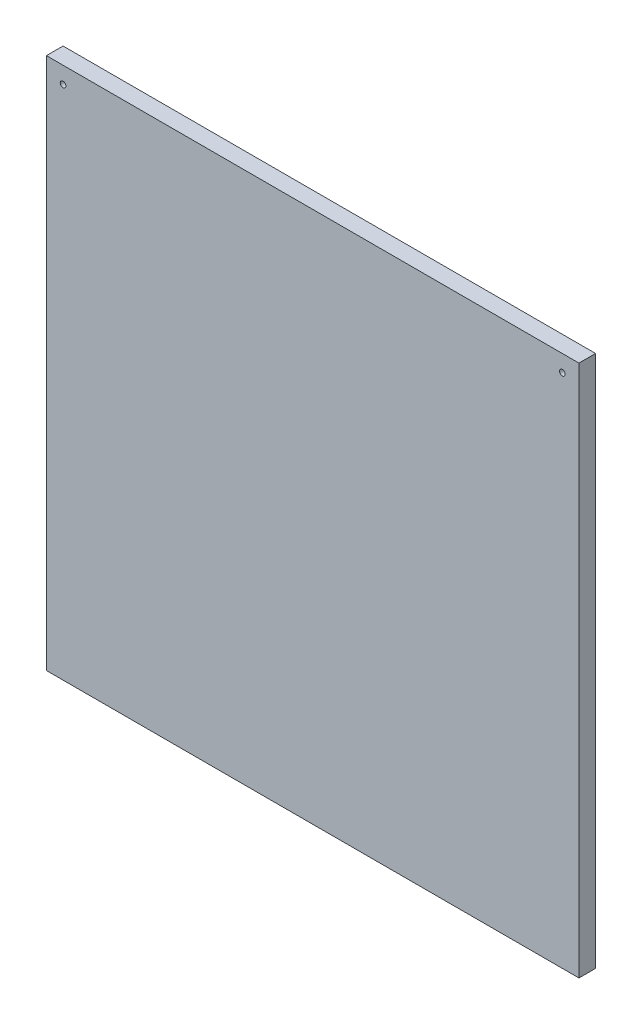
SolidWorks part; units mm, degrees
ref_plane "前视基准面" through (0, 0, 0) normal (0, 0, 1) x (1, 0, 0)
ref_plane "上视基准面" through (0, 0, 0) normal (0, 1, 0) x (1, 0, 0)
ref_plane "右视基准面" through (0, 0, 0) normal (1, 0, 0) x (0, 0, -1)
other "Configuration Table"
sketch "Sketch1" plane through (0, 0, 0) normal (0, 0, 1) x (1, 0, 0)
  line L1 (-400, -400) -> (400, -400)
  line L2 (-400, -400) -> (-400, 400)
  line L3 (-400, 400) -> (400, 400)
  line L4 (400, -400) -> (400, 400)
  line L5 (-400, -400) -> (400, 400) construction
  line L6 (-400, 400) -> (400, -400) construction
  point P0 (0, 0)
extrude "Boss-Extrude1" add sketch "Sketch1" along normal blind 25
ref_plane "Plane1" through (0, 0, 25) normal (0, 0, 1) x (1, 0, 0)
sketch "Sketch2" plane through (0, 0, 25) normal (0, 0, 1) x (1, 0, 0)
  circle A0 centre (375, 375) radius 4.25
  circle A1 centre (-375, 375) radius 4.25
extrude "Cut-Extrude1" cut sketch "Sketch2" against normal blind 25
ref_plane "top_face" through (0, 0, 25) normal (0, 0, 1) x (1, 0, 0)
ref_plane "bottom_face" through (0, 0, 0) normal (0, 0, 1) x (1, 0, 0)
sketch3d "3DSketch1"
  line L0 (-375, 375, 0) -> (-375, 375, 25) construction
ref_axis "hole_axis_1" through (-375, 375, 0) along (0, 0, 1)
sketch3d "3DSketch2"
  line L0 (375, 375, 0) -> (375, 375, 25) construction
ref_axis "hole_axis_2" through (375, 375, 0) along (0, 0, 1)
sketch3d "3DSketch3"
  line L0 (-375, -375, 0) -> (-375, -375, 25) construction
ref_axis "hole_axis_3" through (-375, -375, 0) along (0, 0, 1)
sketch3d "3DSketch4"
  line L0 (375, -375, 0) -> (375, -375, 25) construction
ref_axis "hole_axis_4" through (375, -375, 0) along (0, 0, 1)
